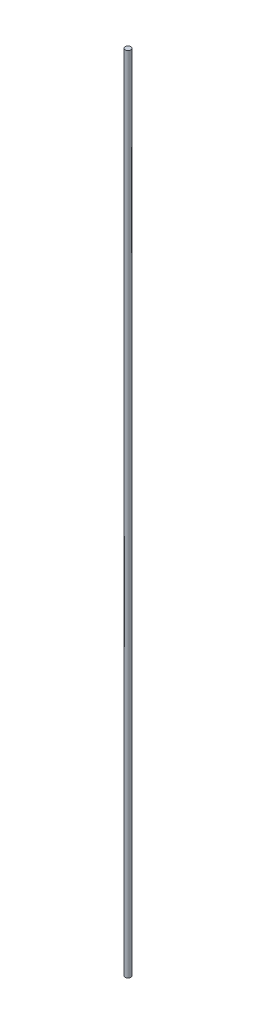
SolidWorks part; units mm, degrees
ref_plane "Спереди" through (0, 0, 0) normal (0, 0, 1) x (1, 0, 0)
ref_plane "Сверху" through (0, 0, 0) normal (0, 1, 0) x (1, 0, 0)
ref_plane "Справа" through (0, 0, 0) normal (1, 0, 0) x (0, 0, -1)
sketch "Эскиз2" plane through (0, 0, 0) normal (0, 0, 1) x (1, 0, 0)
  line L0 (0, 224.6485) -> (-5, 224.6485) construction
  line L5 (-2.5, 224.6485) -> (0, 224.6485)
  line L6 (-2.5, 224.6485) -> (-2.5, -481.2015)
  line L7 (-2.5, -481.2015) -> (0, -481.2015)
  line L8 (0, 224.6485) -> (0, -481.2015)
  line L9 (-2.5, 224.6485) -> (0, -481.2015) construction
  line L10 (-2.5, -481.2015) -> (0, 224.6485) construction
  line L13 (-46.7447, -481.2015) -> (-27.5409, -481.2015) construction
  point P0 (-1.25, -128.2765)
  point P12 (0, 0)
  dimension "D1" = 2.5
revolve "Повернуть1" add sketch "Эскиз2" angle 360 about L6
equation "\"Ширина груза\"= 420"
equation "\"Глубина груза\"= 490"
equation "\"Высота груза\"= 297"
equation "\"Ширина ячейки\"= \"Ширина груза\" + 10"
equation "\"Глубина ячейки\"= \"Глубина груза\" + 10"
equation "\"Высота ячейки\"= \"Высота груза\" + 10 + 13"
equation "\"Колво ячеек ширина\"= 2"
equation "\"Колво ячеек высота\"= 2"
equation "\"Толщина стенки\" = 6"
equation "\"Крепление дверцы\"= 5"
equation "\"Ширина рейки\"= \"Толщина шестерни\""
equation "\"Высота рейки\"= 20"
equation "\"Высота пола\"= 20"
equation "\"Колво полозьев\"= 5"
equation "\"Отступ рейки\"= 20"
equation "\"Глубина каретки\"= \"Глубина ячейки\" + 30 + \"Мотор Y высота корпуса\" + 20"
equation "\"Длинна рейки\"= ( \"Ширина ячейки\" + \"Толщина стенки\" + \"Крепление дверцы\" ) * \"Колво ячеек ширина\" + \"Ширина ячейки выгрузки\" * \"Колво выгрузки\" + \"Толщина стенки\""
equation "\"Отступ шпильки\"= 26"
equation "\"Диаметр шпильки\"= 5"
equation "\"Длинна шпильки\"= ( \"Высота ячейки\" + \"Толщина стенки\" + \"Высота пола\" ) * \"Колво ячеек высота\" + ( \"Толщина стенки\" + \"Отступ рейки\" ) * 2 "
equation "\"D1@Эскиз2\"= \"Диаметр шпильки\" / 2"
equation "\"Ширина пластины\"= 50  "
equation "\"Высота зона выгрузки\"= \"Высота ячейки\" * 2 + \"Толщина стенки\" * 2"
equation "\"Колво выгрузки\"= 1"
equation "\"Отступ крепления мотора фиксации\" = 30"
equation "\"Мотор X ширина корпуса\"= 42.3"
equation "\"Мотор X высота корпуса\"= 42.3"
equation "\"Мотор X длина корпуса\"= 40"
equation "\"Мотор X вылет вала\"= 19.8"
equation "\"Мотор Y ширина корпуса\"= 42.3"
equation "\"Мотор Y высота корпуса\"= 42.3"
equation "\"Мотор Y длина корпуса\"= 48"
equation "\"Мотор Y вылет вала\"= 30"
equation "\"Мотор Z ширина корпуса\"= 42"
equation "\"Мотор Z высота корпуса\"= 42"
equation "\"Мотор Z длина корпуса\"= 40"
equation "\"Мотор Z вылет вала\"= 23"
equation "\"Мотор диаметр вала ПРЕДВ\"= 5"
equation "\"Мотор шаг крепления ПРЕДВ\"= 31"
equation "\"Мотор диаметр отверстий ПРЕДВ\"= 3"
equation "\"Мотор глубина отверстий ПРЕДВ\"= 4.5"
equation "\"Мотор диаметр буртика ПРЕДВ\"= 22"
equation "\"Мотор высота буртика ПРЕДВ\"= 2"
equation "\"Мотор диаметр шкива ПРЕДВ\"= 16"
equation "\"Мотор длина шкива ПРЕДВ\"= 12"
equation "\"Мотор отступ шкива ПРЕДВ\"= 5"
equation "\"Мотор X шаг градусов\"= 1.8"
equation "\"Мотор X ток А\"= 1.5"
equation "\"Мотор X сопротивление Ом\"= 1.3"
equation "\"Мотор X индуктивность мГн\"= 2"
equation "\"Мотор Y шаг градусов\"= 1.8"
equation "\"Мотор Y ток А\"= 2.2"
equation "\"Мотор Y сопротивление Ом\"= 0.9"
equation "\"Мотор Y индуктивность мГн\"= 2"
equation "\"Мотор Z шаг градусов\"= 1.8"
equation "\"Мотор Z ток А\"= 1"
equation "\"Мотор Z сопротивление Ом\"= 4"
equation "\"Мотор Z индуктивность мГн\"= 8"
equation "\"Мотор Y диаметр ротора\"= 25.78"
equation "\"Ширина ячейки выгрузки\"= \"Ширина ячейки\" + \"Толщина стенки\" + \"Отступ крепления мотора фиксации\"*2"
